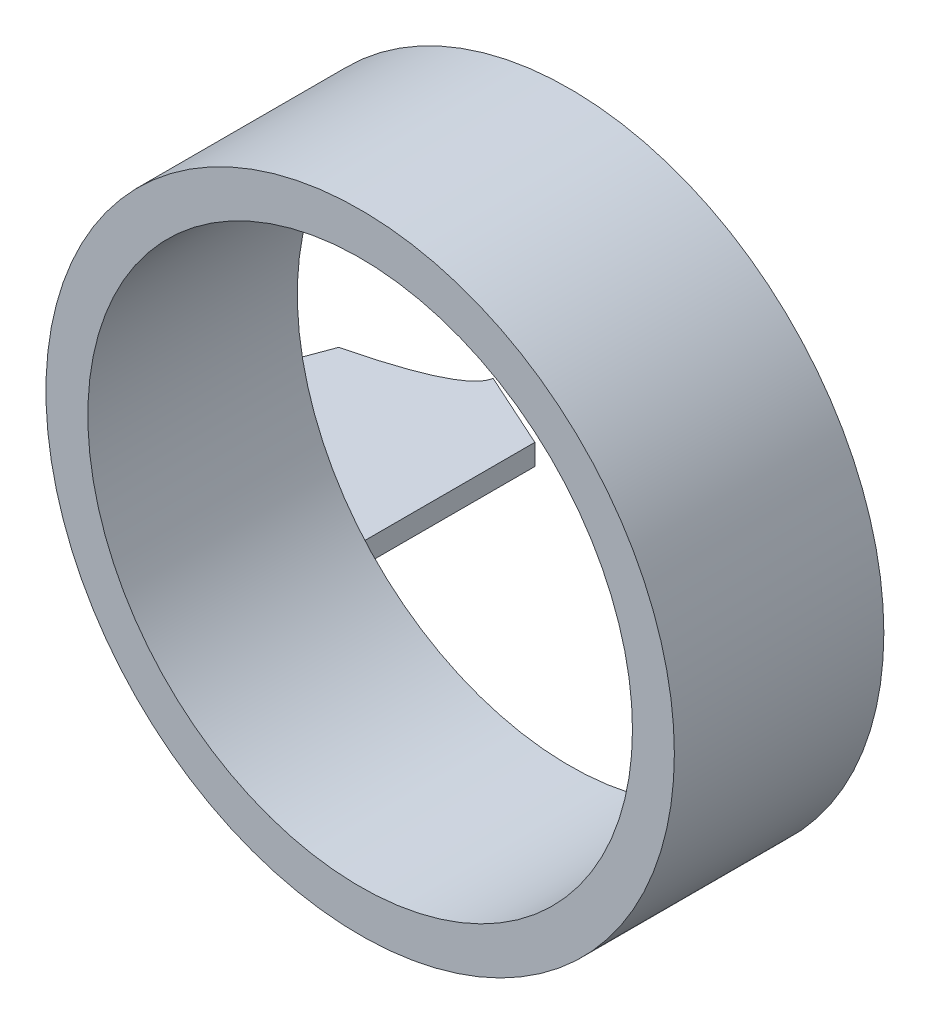
SolidWorks part; units mm, degrees
ref_plane "Front Plane" through (0, 0, 0) normal (0, 0, 1) x (1, 0, 0)
ref_plane "Top Plane" through (0, 0, 0) normal (0, 1, 0) x (1, 0, 0)
ref_plane "Right Plane" through (0, 0, 0) normal (1, 0, 0) x (0, 0, -1)
sketch "Sketch1" plane through (0, 0, 0) normal (0, 0, 1) x (1, 0, 0)
  circle A1 centre (0, 0) radius 30
  dimension "D1" = 60
extrude "Boss-Extrude1" add sketch "Sketch1" along normal blind 10 and the other way blind 10 contours A1
sketch "Sketch2" plane through (0, 0, 10) normal (0, 0, 1) x (1, 0, 0)
  circle A0 centre (0, 0) radius 26
  dimension "D1" = 52
extrude "Cut-Extrude1" cut sketch "Sketch2" against normal blind 20 and the other way blind 10
ref_plane "Plane1" through (0, -20, 0) normal (0, 1, 0) x (1, 0, 0)
sketch "Sketch7" plane through (0, -20, 0) normal (0, 1, 0) x (1, 0, 0)
  line L10 (-39.6267, 12.5892) -> (-30.0548, 10.2478) construction
  line L11 (-30.0548, 10.2478) -> (-29.698, 7.7887) construction
  line L19 (-29.698, 7.7887) -> (-22.4106, 11.0892)
  line L24 (-22.4106, 11.0892) -> (-22.4106, 29.0892)
  line L27 (-42.4106, 20.0892) -> (-39.6267, 12.5892)
  line L28 (-29.698, 32.3897) -> (-22.4106, 29.0892)
  line L29 (-39.6267, 27.5892) -> (-30.0548, 29.9306) construction
  line L30 (-30.0548, 29.9306) -> (-29.698, 32.3897) construction
  line L31 (-42.4106, 20.0892) -> (-39.6267, 27.5892)
  spline S0 degree 2 poles (-39.6267, 12.5892) (-30.0548, 10.2478) (-29.698, 7.7887) knots 0 0 0 1 1 1
  spline S1 degree 2 poles (-39.6267, 27.5892) (-30.0548, 29.9306) (-29.698, 32.3897) knots 0 0 0 1 1 1
  point P2 (0, 0)
  dimension "D3" = 8
  dimension "D1" = 18
  dimension "D2" = 8
  dimension "D4" = 8
  dimension "D5" = 112
  dimension "D6" = 15
extrude "Boss-Extrude3" add sketch "Sketch7" against normal blind 2 contours L31 S1 L28 L24 L19 S0 L27
